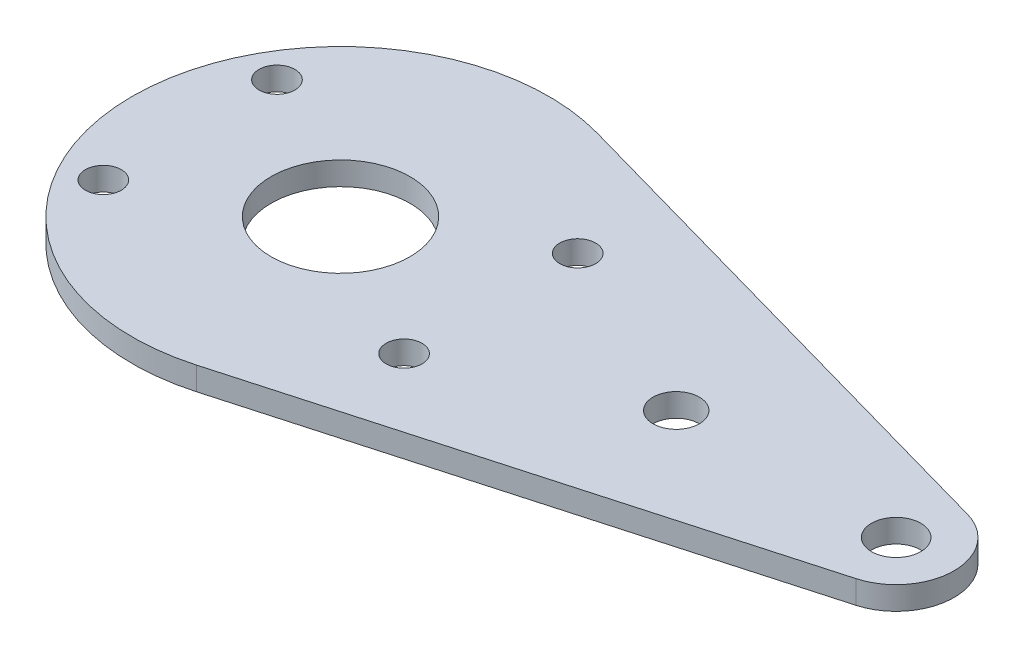
SolidWorks part; units mm, degrees
material "6061-T6 (SS)"
ref_plane "Front" through (0, 0, 0) normal (0, 0, 1) x (1, 0, 0)
ref_plane "Top" through (0, 0, 0) normal (0, 1, 0) x (1, 0, 0)
ref_plane "Right" through (0, 0, 0) normal (1, 0, 0) x (0, 0, -1)
sketch "Sketch1" plane through (0, 0, 0) normal (0, 1, 0) x (1, 0, 0)
  line L0 (7.7391, 27.507) -> (78.3497, 7.6408)
  line L7 (7.7391, -27.507) -> (78.3497, -7.6408)
  circle A0 centre (0, 0) radius 28.575
  circle A1 centre (0, 0) radius 9.525
  circle A2 centre (76.2, 0) radius 7.9375
  circle A3 centre (76.2, 0) radius 3.3782
  point P5 (104.9782, -16.4919)
  point P7 (10.2613, 24.9606)
  point P8 (0, 0)
  point P9 (0, 0)
  point P10 (8.0671, 25.7536)
  point P11 (14.5113, -28.2931)
  point P14 (0, 0)
  point P15 (0, 0)
  point P18 (103.5402, -10.9283)
  point P19 (0, 0)
  dimension "D2" = 57.15
  dimension "D3" = 15.875
  dimension "D4" = 6.7564
  dimension "D1" = 19.05
  dimension "D5" = 76.2
extrude "Boss-Extrude1" add sketch "Sketch1" along normal blind 3.175 contours A2 L0 A0 L7 | A0 | A2 A3 region at (44.3224, 0, 0) region at (22.1337, 0, -16.7658) region at (82.3483, 0, -4.6572)
sketch "Sketch4" plane through (0, 3.175, 0) normal (0, 1, 0) x (1, 0, 0)
  circle A0 centre (0, 0) radius 23.8125
  point P7 (-20.6222, 11.9062)
  point P9 (20.6222, 11.9062)
  point P11 (20.6222, -11.9062)
  point P13 (-20.6222, -11.9062)
  dimension "D1" = 47.625
  dimension "D2" = 23.8125
hole_wizard "#10 (0.1935) Diameter Hole1" positions "Sketch4" profile "Sketch3" hole size "#10" standard "ANSI Inch" end condition through all
sketch "Sketch3" plane through (-20.6222, 3.175, 11.9062) normal (1, 0, 0) x (0, 0, 1)
  line L0 (0, 0) -> (0, 3.175)
  line L1 (0, 3.175) -> (2.4574, 3.175)
  line L2 (2.4574, 3.175) -> (2.4574, 0)
  line L5 (2.4574, 0) -> (0, 0)
  line L11 (0, -6.35) -> (0, 107.95) construction
  dimension "Thru Hole Dia." = 4.9149
  dimension "Thru Hole Depth" = 3.175
sketch "Sketch7" plane through (0, 3.175, 0) normal (0, 1, 0) x (1, 0, 0)
  arc A0 (78.3497, -7.6408) -> (78.3497, 7.6408) centre (76.2, 0) ccw construction
  point P0 (46.0375, 0)
  point P4 (48.2797, 0)
  point P8 (84.1375, 0)
  dimension "D1" = 38.1
hole_wizard "1/4 (0.25) Diameter Hole2" positions "Sketch7" profile "Sketch8" hole size "1/4" standard "ANSI Inch" end condition through all
sketch "Sketch8" plane through (46.0375, 3.175, 0) normal (1, 0, 0) x (0, 0, 1)
  line L0 (0, 0) -> (0, 3.175)
  line L1 (0, 3.175) -> (3.175, 3.175)
  line L2 (3.175, 3.175) -> (3.175, 0)
  line L5 (3.175, 0) -> (0, 0)
  line L11 (0, -6.35) -> (0, 107.95) construction
  dimension "Thru Hole Dia." = 6.35
  dimension "Thru Hole Depth" = 3.175
